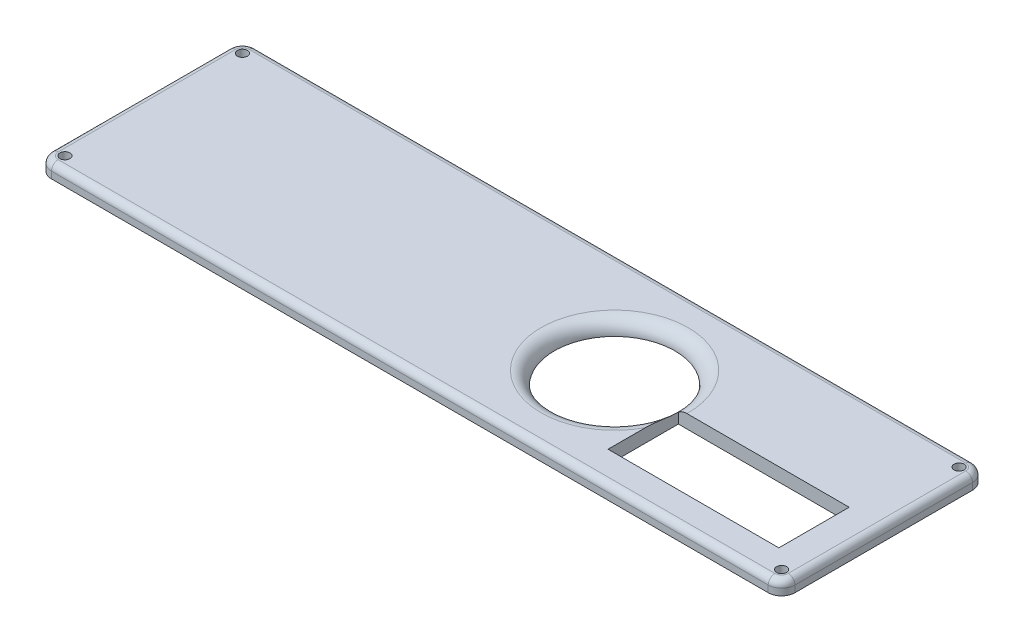
SolidWorks part; units mm, degrees
ref_plane "Front Plane" through (0, 0, 0) normal (0, 0, 1) x (1, 0, 0)
ref_plane "Top Plane" through (0, 0, 0) normal (0, 1, 0) x (1, 0, 0)
ref_plane "Right Plane" through (0, 0, 0) normal (1, 0, 0) x (0, 0, -1)
sketch "Sketch1" plane through (0, 0, 0) normal (0, 1, 0) x (1, 0, 0)
  line L1 (0, 0) -> (111, 0)
  line L2 (0, 0) -> (0, 30.5)
  line L3 (0, 30.5) -> (111, 30.5)
  line L4 (111, 0) -> (111, 30.5)
  dimension "D1" = 30.5
  dimension "D2" = 111
extrude "Boss-Extrude1" add sketch "Sketch1" along normal blind 2
sketch "Sketch2" plane through (0, 2, 0) normal (0, 1, 0) x (1, 0, 0)
  line L0 (0, 30.5) -> (0, 0) construction
  line L1 (111, 30.5) -> (0, 30.5) construction
  line L2 (0, 0) -> (111, 0) construction
  line L3 (111, 0) -> (111, 30.5) construction
  line L4 (80.49, 4.6) -> (105.99, 15.1) construction
  line L5 (80.49, 4.6) -> (105.99, 4.6)
  line L6 (80.49, 4.6) -> (80.49, 15.1)
  line L7 (80.49, 15.1) -> (105.99, 15.1)
  line L8 (105.99, 4.6) -> (105.99, 15.1)
  circle A0 centre (2, 28.5) radius 0.75
  circle A1 centre (2, 2) radius 0.75
  circle A2 centre (109, 2) radius 0.75
  circle A3 centre (109, 28.5) radius 0.75
  circle A4 centre (70.76, 15.31) radius 9
  point P22 (78, 23.82)
  point P23 (93.24, 9.85)
  dimension "D1" = 1.5
  dimension "D18" = 18
  dimension "D2" = 2
  dimension "D3" = 2
  dimension "D4" = 2
  dimension "D5" = 2
  dimension "D6" = 2
  dimension "D7" = 2
  dimension "D8" = 2
  dimension "D9" = 2
  dimension "D10" = 6.68
  dimension "D11" = 33
  dimension "D12" = 8.51
  dimension "D13" = 7.24
  dimension "D14" = 10.5
  dimension "D15" = 25.5
  dimension "D16" = 15.24
  dimension "D17" = 13.97
extrude "Cut-Extrude1" cut sketch "Sketch2" against normal through all
fillet "Fillet1" radius 1 4 edges at (55.5, 2, -30.5) (111, 2, -15.25) (55.5, 2, 0) (0, 2, -15.25)
fillet "Fillet2" radius 2 9 edges at (110.7071, 1.7071, -0.2929) (110.7071, 1.7071, -30.2071) (0.2929, 1.7071, -30.2071) (0.2929, 1.7071, -0.2929) (0, 0.5, 0) (0, 0.5, -30.5) (111, 0.5, -30.5) (111, 0.5, 0) (70.76, 2, -6.31)
